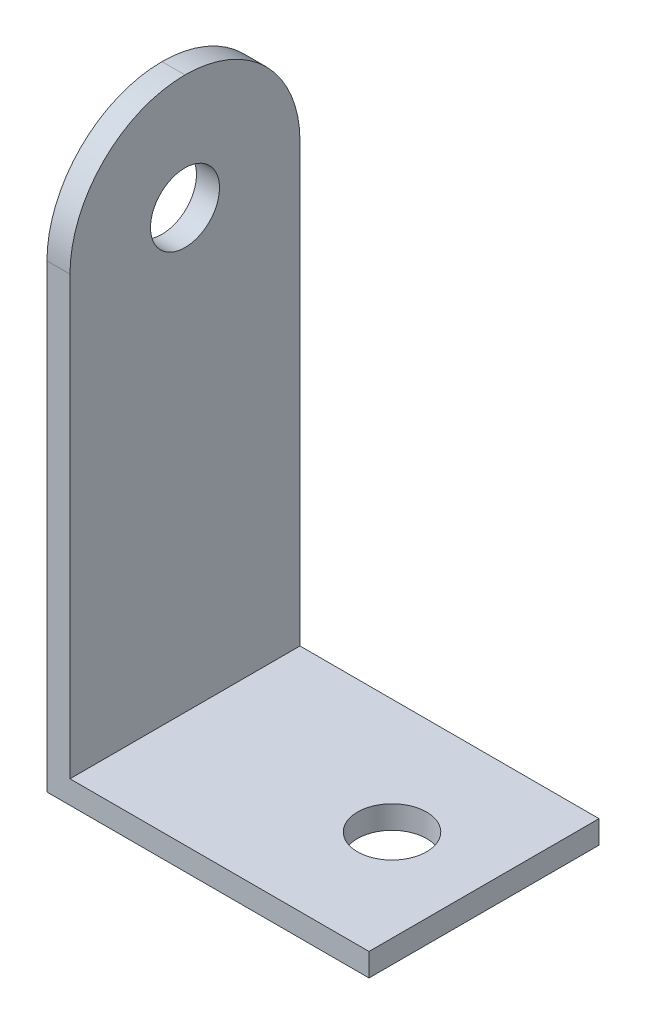
SolidWorks part; units mm, degrees
ref_plane "Front" through (0, 0, 0) normal (0, 0, 1) x (1, 0, 0)
ref_plane "Top" through (0, 0, 0) normal (0, 1, 0) x (1, 0, 0)
ref_plane "Right" through (0, 0, 0) normal (1, 0, 0) x (0, 0, -1)
sketch "Sketch1" plane through (0, 0, 0) normal (0, 0, 1) x (1, 0, 0)
  line L0 (0, 0) -> (0, 25)
  line L1 (0, 25) -> (1, 25)
  line L2 (1, 25) -> (1, 1)
  line L3 (1, 1) -> (14, 1)
  line L4 (14, 1) -> (14, 0)
  line L5 (14, 0) -> (0, 0)
  dimension "D1" = 1
  dimension "D2" = 1
  dimension "D3" = 24
  dimension "D4" = 13
extrude "Boss-Extrude1" add sketch "Sketch1" along normal blind 10
fillet "Fillet1" radius 5 2 edges at (0.5, 25, 0) (0.5, 25, 10)
ref_plane "Plane1" through (1, 0, 0) normal (1, 0, 0) x (0, 0, -1)
sketch "Sketch2" plane through (1, 0, 0) normal (1, 0, 0) x (0, 0, -1)
  circle A0 centre (-5, 20) radius 1.5
  dimension "D1" = 3
extrude "Cut-Extrude1" cut sketch "Sketch2" against normal through all contours A0
ref_plane "Plane2" through (0, 1, 0) normal (0, 1, 0) x (1, 0, 0)
sketch "Sketch3" plane through (0, 1, 0) normal (0, 1, 0) x (1, 0, 0)
  line L0 (14, 0) -> (1, 0) construction
  line L1 (14, -10) -> (14, 0) construction
  circle A0 centre (10, -5) radius 1.5
  dimension "D1" = 3
  dimension "D2" = 5
  dimension "D3" = 4
extrude "Cut-Extrude2" cut sketch "Sketch3" against normal through all contours A0
